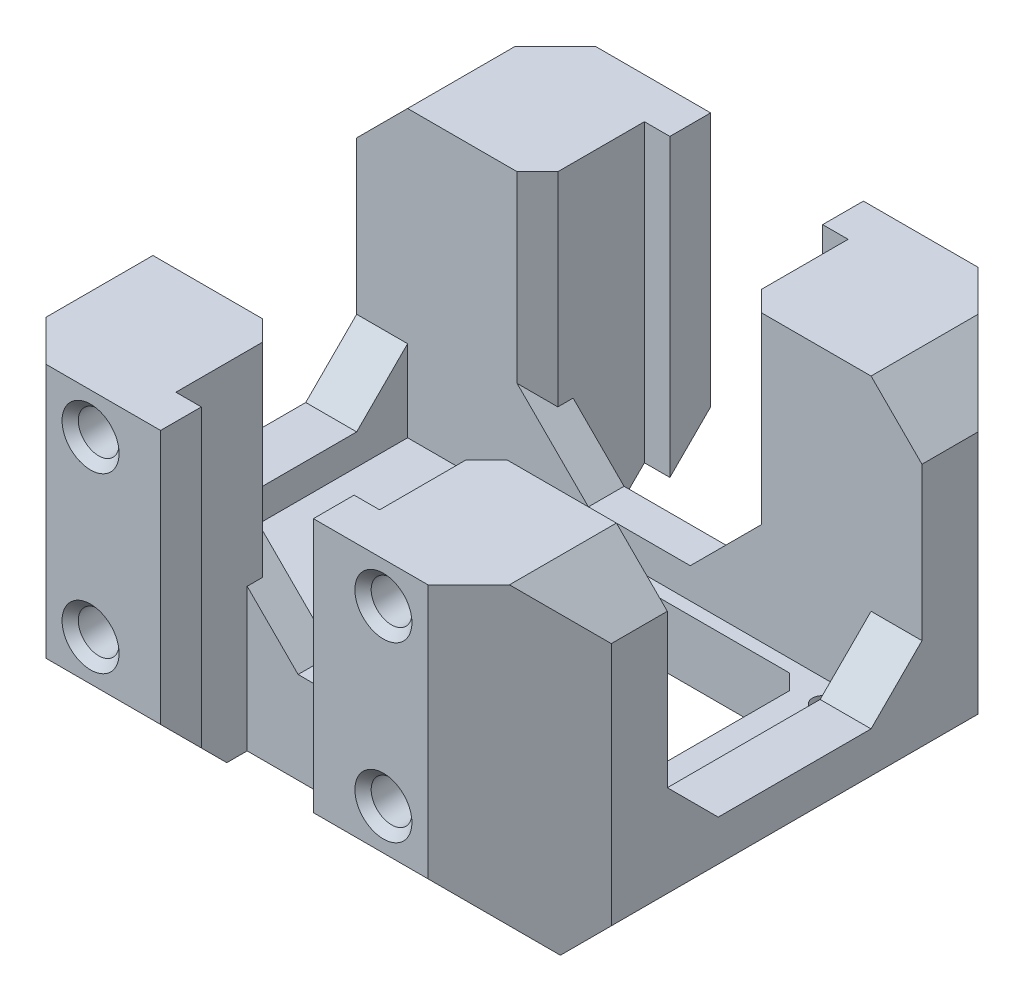
SolidWorks part; units mm, degrees
ref_plane "Front Plane" through (0, 0, 0) normal (0, 0, 1) x (1, 0, 0)
ref_plane "Top Plane" through (0, 0, 0) normal (0, 1, 0) x (1, 0, 0)
ref_plane "Right Plane" through (0, 0, 0) normal (1, 0, 0) x (0, 0, -1)
sketch "Sketch1" plane through (0, 0, 0) normal (0, 1, 0) x (1, 0, 0)
  line L0 (-27.75, -17.5) -> (-27.75, 17.5)
  line L1 (-22.75, -12.5) -> (22.75, -12.5)
  line L2 (-22.75, -12.5) -> (-22.75, 12.5)
  line L3 (-22.75, 12.5) -> (22.75, 12.5)
  line L4 (22.75, -12.5) -> (22.75, 12.5)
  line L5 (-22.75, -12.5) -> (22.75, 12.5) construction
  line L6 (-22.75, 12.5) -> (22.75, -12.5) construction
  line L7 (-27.75, 17.5) -> (27.75, 17.5)
  line L8 (27.75, -17.5) -> (27.75, 17.5)
  line L9 (-27.75, -17.5) -> (27.75, -17.5)
  point P0 (0, 0)
  dimension "D1" = 45.5
  dimension "D2" = 25
  dimension "D3" = 5
extrude "Boss-Extrude1" add sketch "Sketch1" along normal blind 28
sketch "Sketch2" plane through (0, 0, 0) normal (0, -1, 0) x (1, 0, 0)
  line L0 (-27.75, 17.5) -> (27.75, 17.5) construction
  line L1 (-27.75, 17.5) -> (27.75, 17.5)
  line L2 (-27.75, -17.5) -> (-27.75, 17.5) construction
  line L3 (27.75, -17.5) -> (-27.75, -17.5) construction
  line L4 (27.75, 17.5) -> (27.75, -17.5) construction
  line L5 (-27.75, -17.5) -> (-27.75, 17.5)
  line L6 (27.75, -17.5) -> (-27.75, -17.5)
  line L7 (27.75, 17.5) -> (27.75, -17.5)
extrude "Boss-Extrude2" add sketch "Sketch2" along normal blind 6
sketch "Sketch4" plane through (0, 0, 0) normal (0, 1, 0) x (1, 0, 0)
  line L0 (22.75, -12.5) -> (22.75, 12.5) construction
  line L1 (-4.2, -10.25) -> (20.25, -10.25) construction
  line L2 (-4.2, -10.25) -> (-4.2, 10.25) construction
  line L3 (-4.2, 10.25) -> (20.25, 10.25) construction
  line L4 (20.25, -10.25) -> (20.25, 10.25) construction
  line L5 (-4.2, -10.25) -> (20.25, 10.25) construction
  line L6 (-4.2, 10.25) -> (20.25, -10.25) construction
  circle A0 centre (-4.2, 10.25) radius 1
  circle A1 centre (20.25, 10.25) radius 1
  circle A2 centre (20.25, -10.25) radius 1
  circle A3 centre (-4.2, -10.25) radius 1
  point P0 (8.025, 0)
  dimension "D1" = 2
  dimension "D2" = 20.5
  dimension "D3" = 24.45
  dimension "D4" = 2.5
extrude "Cut-Extrude1" cut sketch "Sketch4" against normal blind 3.5
sketch "Sketch5" plane through (0, -3.5, 0) normal (0, 1, 0) x (1, 0, 0)
  circle A0 centre (-4.2, 10.25) radius 2
  circle A1 centre (20.25, 10.25) radius 2
  circle A2 centre (20.25, -10.25) radius 2
  circle A3 centre (-4.2, -10.25) radius 2
  dimension "D1" = 4
extrude "Cut-Extrude2" cut sketch "Sketch5" against normal up to next
sketch "Sketch6" plane through (0, 0, 0) normal (0, 1, 0) x (1, 0, 0)
  line L1 (-1.75, -11.25) -> (17.5, -11.25)
  line L2 (-1.75, -11.25) -> (-1.75, 11.25)
  line L3 (-1.75, 11.25) -> (17.5, 11.25)
  line L4 (17.5, -11.25) -> (17.5, 11.25)
  line L5 (-1.75, -11.25) -> (17.5, 11.25) construction
  line L6 (-1.75, 11.25) -> (17.5, -11.25) construction
  circle A0 centre (20.25, 10.25) radius 1 construction
  point P0 (7.875, 0)
  dimension "D1" = 22.5
  dimension "D2" = 19.25
  dimension "D3" = 2.75
extrude "Cut-Extrude3" cut sketch "Sketch6" against normal up to next
chamfer "Chamfer1" distance 1.5 angle 45 4 edges at (-1.75, -3, 11.25) (17.5, -3, 11.25) (-1.75, -3, -11.25) (17.5, -3, -11.25)
sketch "Sketch7" plane through (0, 0, 0) normal (0, 1, 0) x (1, 0, 0)
  line L0 (-1.75, 9.75) -> (-1.75, -9.75) construction
  circle A0 centre (-12.5, 0) radius 3
  dimension "D1" = 6
  dimension "D2" = 10.75
extrude "Cut-Extrude4" cut sketch "Sketch7" against normal up to next
chamfer "Chamfer2" distance 1 angle 45 2 edges at (-12.5, -6, 3) (-12.5, 0, 3)
sketch "Sketch8" plane through (0, 28, 0) normal (0, 1, 0) x (1, 0, 0)
  line L6 (27.75, -17.5) -> (27.75, 17.5) construction
  line L7 (-27.75, -17.5) -> (27.75, -17.5)
  line L8 (-27.75, -17.5) -> (-27.75, -27)
  line L9 (-27.75, -27) -> (27.75, -27)
  line L10 (27.75, -17.5) -> (27.75, -27)
  dimension "D1" = 9.5
extrude "Boss-Extrude3" add sketch "Sketch8" against normal up to surface (34 mm away) up to face at (-12.5, -6, 4)
sketch "Sketch10" plane through (0, 28, 0) normal (0, 1, 0) x (1, 0, 0)
  line L0 (-27.75, -27) -> (27.75, -27) construction
  line L1 (-10, -16) -> (10, -16)
  line L2 (-10, -16) -> (-10, -23)
  line L3 (-10, -23) -> (10, -23)
  line L4 (10, -16) -> (10, -23)
  line L5 (-10, -16) -> (10, -23) construction
  line L6 (-10, -23) -> (10, -16) construction
  line L7 (-7.5, -27) -> (7.5, -27)
  line L8 (-7.5, -27) -> (-7.5, -23)
  line L9 (-7.5, -23) -> (7.5, -23)
  line L10 (7.5, -27) -> (7.5, -23)
  line L11 (-7.5, -27) -> (7.5, -23) construction
  line L12 (-7.5, -23) -> (7.5, -27) construction
  point P0 (0, -19.5)
  point P5 (0, -25)
  point P15 (-7.5, -25)
  line M10 (-27.75, -27) -> (27.75, -27)
  dimension "D1" = 7
  dimension "D2" = 20
  dimension "D3" = 15
  dimension "D4" = 4
extrude "Cut-Extrude5" cut sketch "Sketch10" against normal up to next contours L4 L1 L2 L3 | L10 L3 L8 M10 region at (0, 28, 19.5) region at (0, 28, 25)
mirror "Mirror3" about plane through (0, 0, 0) normal (0, 0, 1) of "Cut-Extrude5", "Boss-Extrude3"
chamfer "Chamfer7" distance 9 angle 45 8 edges at (17.625, -6, -27) (27.75, 11, -27) (-17.625, -6, -27) (-27.75, 11, -27) (17.625, -6, 27) (27.75, 11, 27) (-17.625, -6, 27) (-27.75, 11, 27)
chamfer "Chamfer8" distance 5 angle 45 2 edges at (27.75, 28, 0) (-27.75, 28, 0)
chamfer "Chamfer9" distance 5 angle 45 2 edges at (27.75, -6, 0) (-27.75, -6, 0)
sketch "Sketch12" plane through (0, 0, -27) normal (0, 0, -1) x (-1, 0, 0)
  line L0 (18.75, 28) -> (7.5, 28) construction
  line L1 (-14.375, 7) -> (14.375, 7) construction
  line L2 (-14.375, 7) -> (-14.375, 24) construction
  line L3 (-14.375, 24) -> (14.375, 24) construction
  line L4 (14.375, 7) -> (14.375, 24) construction
  line L5 (-14.375, 7) -> (14.375, 24) construction
  line L6 (-14.375, 24) -> (14.375, 7) construction
  line L7 (7.5, 3) -> (18.75, 3) construction
  circle A0 centre (-14.375, 24) radius 1.45
  circle A1 centre (14.375, 24) radius 1.45
  circle A2 centre (14.375, 7) radius 1.45
  circle A3 centre (-14.375, 7) radius 1.45
  point P0 (0, 15.5)
  dimension "D1" = 2.9
  dimension "D3" = 4
  dimension "D4" = 4
  dimension "D2" = 28.75
extrude "Cut-Extrude7" cut sketch "Sketch12" against normal blind 10
mirror "Mirror4" about plane through (0, 0, 0) normal (0, 0, 1) of "Cut-Extrude7"
sketch "Sketch13" plane through (0, 0, -12.5) normal (0, 0, 1) x (1, 0, 0)
  line L0 (10, -6) -> (10, 28) construction
  line L1 (-10, 28) -> (10, 28)
  line L2 (-10, 28) -> (-10, 3)
  line L3 (-10, 3) -> (10, 3)
  line L4 (10, 28) -> (10, 3)
  line L6 (18.75, 3) -> (7.5, 3) construction
extrude "Cut-Extrude8" cut sketch "Sketch13" against normal up to next
sketch "Sketch14" plane through (22.75, 0, 0) normal (-1, 0, 0) x (0, 0, 1)
  line L0 (12.5, 28) -> (12.5, 0) construction
  line L1 (-12.5, 28) -> (12.5, 28)
  line L2 (-12.5, 28) -> (-12.5, 3)
  line L3 (-12.5, 3) -> (12.5, 3)
  line L4 (12.5, 28) -> (12.5, 3)
  line L5 (-16, 3) -> (-12.5, 3) construction
extrude "Cut-Extrude9" cut sketch "Sketch14" against normal up to next
mirror "Mirror5" about plane through (0, 0, 0) normal (1, 0, 0) of "Cut-Extrude9"
mirror "Mirror6" about plane through (0, 0, 0) normal (0, 0, 1) of "Cut-Extrude8"
chamfer "Chamfer10" distance 5 angle 45 8 edges at (-25.25, 3, 12.5) (-25.25, 3, -12.5) (-10, 3, 14.25) (10, 3, 14.25) (25.25, 3, 12.5) (25.25, 3, -12.5) (-10, 3, -14.25) (10, 3, -14.25)
chamfer "Chamfer11" distance 2 angle 45 4 edges at (10, 18, -12.5) (-10, 18, 12.5) (-10, 18, -12.5) (10, 18, 12.5)
sketch "Sketch15" plane through (0, 0, -27) normal (0, 0, -1) x (-1, 0, 0)
  circle A0 centre (-14.375, 24) radius 2
  circle A1 centre (14.375, 24) radius 2
  circle A2 centre (14.375, 7) radius 2
  circle A3 centre (-14.375, 7) radius 2
  dimension "D1" = 4
extrude "Cut-Extrude10" cut sketch "Sketch15" against normal blind 5.2
mirror "Mirror7" about plane through (0, 0, 0) normal (0, 0, 1) of "Cut-Extrude10"
chamfer "Chamfer12" distance 0.8 angle 45 8 edges at (12.375, 7, 27) (12.375, 24, 27) (-16.375, 7, 27) (-16.375, 24, 27) (12.375, 7, -27) (12.375, 24, -27) (-16.375, 7, -27) (-16.375, 24, -27)
